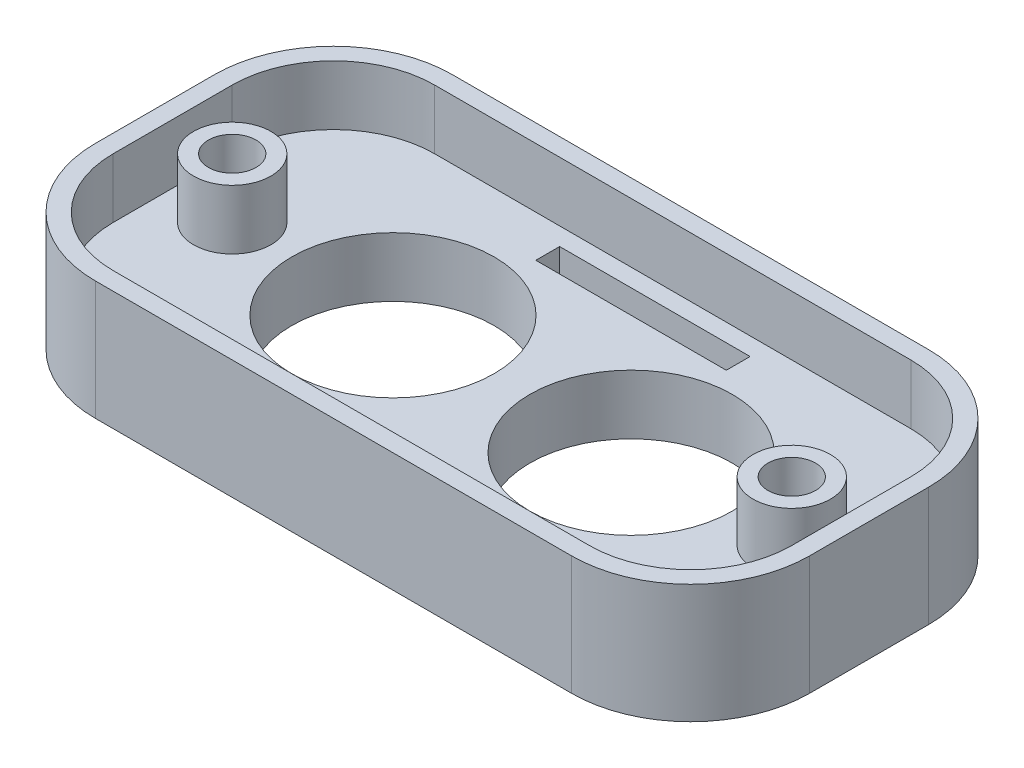
SolidWorks part; units mm, degrees
ref_plane "Спереди" through (0, 0, 0) normal (0, 0, 1) x (1, 0, 0)
ref_plane "Сверху" through (0, 0, 0) normal (0, 1, 0) x (1, 0, 0)
ref_plane "Справа" through (0, 0, 0) normal (1, 0, 0) x (0, 0, -1)
sketch "Эскиз1" plane through (0, 0, 0) normal (0, 1, 0) x (1, 0, 0)
  line L0 (-72.8908, 0) -> (73.0919, 0) construction
  line L1 (0, 46.6177) -> (0, -43.256) construction
  line L3 (-20, 15) -> (20, 15)
  line L4 (-30, 5) -> (-30, -5)
  line L5 (-20, -15) -> (20, -15)
  line L6 (30, 5) -> (30, -5)
  circle A0 centre (-10, 0) radius 8.5
  circle A1 centre (10, 0) radius 8.5
  arc A2 (20, 15) -> (30, 5) centre (20, 5) cw
  arc A3 (20, -15) -> (30, -5) centre (20, -5) ccw
  arc A4 (-30, -5) -> (-20, -15) centre (-20, -5) ccw
  arc A5 (-20, 15) -> (-30, 5) centre (-20, 5) ccw
  point P19 (-30, -15)
  point P22 (-30, 15)
  dimension "D1" = 17
  dimension "D2" = 10
  dimension "D3" = 15
  dimension "D7" = 10
  dimension "D4" = 30
  dimension "D5" = 30
  dimension "D6" = 30
extrude "Бобышка-Вытянуть1" add sketch "Эскиз1" along normal blind 10
sketch "Эскиз2" plane through (0, 10, 0) normal (0, 1, 0) x (1, 0, 0)
  line L0 (-20, -15) -> (20, -15) construction
  line L1 (30, -5) -> (30, 5) construction
  line L2 (20, 15) -> (-20, 15) construction
  line L3 (-20, -15) -> (20, -15)
  line L4 (30, -5) -> (30, 5)
  line L5 (20, 15) -> (-20, 15)
  line L6 (-30, 5) -> (-30, -5) construction
  line L7 (-30, 5) -> (-30, -5)
  line L8 (-20, 13.5) -> (20, 13.5)
  line L9 (-20, -13.5) -> (20, -13.5)
  line L10 (-20, 13.5) -> (-20, -13.5) construction
  line L11 (-28.5, 5) -> (-28.5, -5)
  line L12 (0, 19.9133) -> (0, -21.3858) construction
  line L13 (28.5, 5) -> (28.5, -5)
  arc A0 (-30, -5) -> (-20, -15) centre (-20, -5) ccw construction
  arc A1 (20, -15) -> (30, -5) centre (20, -5) ccw construction
  arc A2 (30, 5) -> (20, 15) centre (20, 5) ccw construction
  arc A3 (-20, 15) -> (-30, 5) centre (-20, 5) ccw construction
  arc A4 (-30, -5) -> (-20, -15) centre (-20, -5) ccw
  arc A5 (20, -15) -> (30, -5) centre (20, -5) ccw
  arc A6 (30, 5) -> (20, 15) centre (20, 5) ccw
  arc A7 (-20, 15) -> (-30, 5) centre (-20, 5) ccw
  circle A8 centre (-20, 5) radius 8.5
  circle A9 centre (-20, -5) radius 8.5
  circle A10 centre (20, 5) radius 8.5
  circle A11 centre (20, -5) radius 8.5
  point P24 (0, 13.5)
  point P29 (0, -13.5)
  circle M13 centre (-10, 0) radius 8.5
  circle M14 centre (10, 0) radius 8.5
  dimension "D1" = 1.5
  dimension "D2" = 1.5
extrude "Вырез-Вытянуть1" cut sketch "Эскиз2" against normal blind 5 contours A9 A8 M13 | L9 A11 A10 L8 A8 A9 M14 M13 | A9 A8 M13 | A9 A8 M13 | A9 A8 L11 | A11 A10 M14 | A11 A10 M14 | A11 A10 M14 | A10 A11 L13 region at (-21.3769, 10, -7.7477) region at (0, 10, 0) region at (21.3769, 10, -7.7477) region at (-28.0214, 10, 0) region at (28.0214, 10, 0) region at (-21.3769, 10, 7.7477) region at (-21.7512, 10, 0) region at (21.3769, 10, 7.7477) region at (21.7512, 10, 0)
sketch "Эскиз3" plane through (0, 5, 0) normal (0, 1, 0) x (1, 0, 0)
  line L1 (-30, 5) -> (-30, -5) construction
  line L2 (0, 13.5) -> (0, -13.5) construction
  line L3 (-20, 13.5) -> (20, 13.5) construction
  line L4 (-20, -13.5) -> (20, -13.5) construction
  circle A0 centre (-23.5, 0) radius 3.25
  circle A1 centre (-23.5, 0) radius 2
  circle A2 centre (23.5, 0) radius 3.25
  circle A3 centre (23.5, 0) radius 2
  dimension "D1" = 6.5
  dimension "D2" = 6.5
  dimension "D3" = 4
extrude "Бобышка-Вытянуть2" add sketch "Эскиз3" along normal blind 5
sketch "Эскиз4" plane through (0, 5, 0) normal (0, 1, 0) x (1, 0, 0)
  line L0 (0, 13.5) -> (0, -13.5) construction
  line L1 (-8, 12) -> (8, 12)
  line L2 (-8, 12) -> (-8, 10)
  line L3 (-8, 10) -> (8, 10)
  line L4 (8, 12) -> (8, 10)
  line L5 (-20, 13.5) -> (20, 13.5) construction
  line L6 (-20, -13.5) -> (20, -13.5) construction
  line L7 (-28.5, 0) -> (28.5, 0) construction
  line L8 (-28.5, 5) -> (-28.5, -5) construction
  line L9 (28.5, 5) -> (28.5, -5) construction
  line L10 (8, -12) -> (8, -10)
  line L11 (-8, -10) -> (8, -10)
  line L12 (-8, -12) -> (-8, -10)
  line L13 (-8, -12) -> (8, -12)
  point P10 (0, 10)
  dimension "D1" = 2
  dimension "D2" = 8
  dimension "D3" = 1.5
extrude "Вырез-Вытянуть2" cut sketch "Эскиз4" against normal through all
